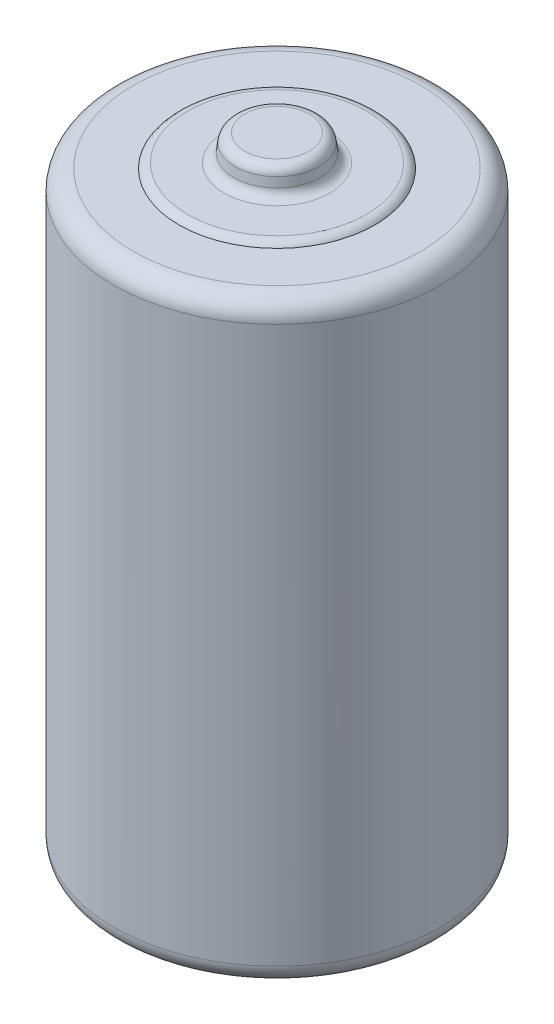
SolidWorks part; units mm, degrees
ref_plane "Front Plane" through (0, 0, 0) normal (0, 0, 1) x (1, 0, 0)
ref_plane "Top Plane" through (0, 0, 0) normal (0, 1, 0) x (1, 0, 0)
ref_plane "Right Plane" through (0, 0, 0) normal (1, 0, 0) x (0, 0, -1)
sketch "Sketch1" plane through (0, 0, 0) normal (0, 0, 1) x (1, 0, 0)
  line L0 (0, 0) -> (0, 49.657) construction
  line L1 (0, 0) -> (-12.7, 0)
  line L2 (-12.7, 0) -> (-12.7, 47.625)
  line L3 (-12.7, 47.625) -> (-3.429, 47.625)
  line L4 (-3.429, 47.625) -> (-3.175, 49.657)
  line L5 (-3.175, 49.657) -> (0, 49.657)
  line L6 (0, 0) -> (0, 49.657)
  dimension "D1" = 25.4
  dimension "D2" = 47.625
  dimension "D3" = 3.175
  dimension "D4" = 2.032
  dimension "D5" = 0.254
revolve "Revolve1" add sketch "Sketch1" angle 360 about L0
sketch "Sketch2" plane through (0, 47.625, 0) normal (0, 1, 0) x (1, 0, 0)
  circle A0 centre (0, 0) radius 12.7 construction
  circle A1 centre (0, 0) radius 12.7
  circle A2 centre (0, 0) radius 7.62
  dimension "D1" = 5.08
extrude "Extrude1" cut sketch "Sketch2" against normal blind 0.381
sketch "Sketch3" plane through (0, 0, 0) normal (0, -1, 0) x (1, 0, 0)
  circle A0 centre (0, 0) radius 9.1186
  circle A1 centre (0, 0) radius 12.7 construction
  circle A2 centre (0, 0) radius 12.7
  dimension "D1" = 18.2372
extrude "Extrude2" cut sketch "Sketch3" against normal blind 0.9652
sketch "Sketch4" plane through (0, 0, 0) normal (0, -1, 0) x (1, 0, 0)
  circle A0 centre (0, 0) radius 3.81
  circle A1 centre (0, 0) radius 5.08
  dimension "D1" = 7.62
  dimension "D2" = 10.16
extrude "Extrude3" cut sketch "Sketch4" against normal blind 0.381
fillet "Fillet1" radius 1.524 3 edges at (0, 0, -9.1186) (0, 0.9652, -12.7) (0, 47.244, 12.7)
fillet "Fillet2" radius 0.762 3 edges at (0, 47.625, 7.62) (0, 47.625, -3.429) (0, 49.657, -3.175)
fillet "Fillet3" radius 0.635 2 edges at (0, 0.381, -3.81) (0, 0.381, -5.08)
